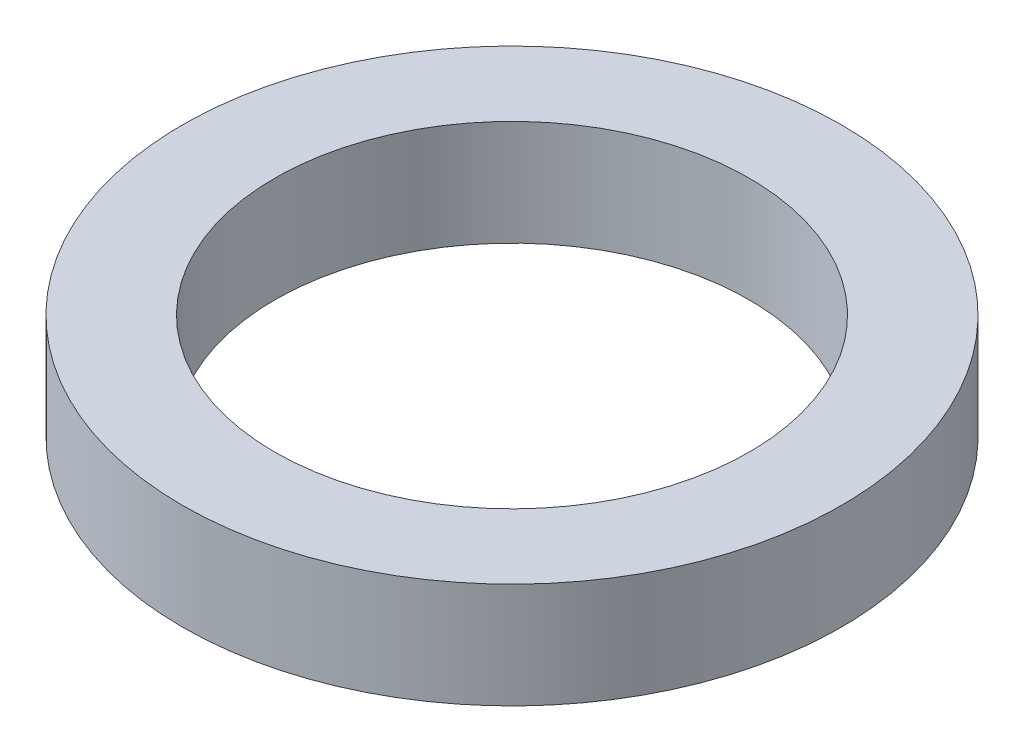
SolidWorks part; units mm, degrees
ref_plane "Front Plane" through (0, 0, 0) normal (0, 0, 1) x (1, 0, 0)
ref_plane "Top Plane" through (0, 0, 0) normal (0, 1, 0) x (1, 0, 0)
ref_plane "Right Plane" through (0, 0, 0) normal (1, 0, 0) x (0, 0, -1)
sketch "Sketch1" plane through (0, 0, 0) normal (0, 1, 0) x (1, 0, 0)
  circle A0 centre (0, 0) radius 62.5
  dimension "FLANGE_OD" = 125
extrude "Boss-Extrude1" add sketch "Sketch1" along normal blind 20
sketch "Sketch2" plane through (0, 0, 0) normal (0, 1, 0) x (1, 0, 0)
  circle A0 centre (0, 0) radius 45
  dimension "BORE_D" = 90
extrude "Cut-Extrude1" cut sketch "Sketch2" along normal through all
sketch "Sketch3" plane through (0, 20, 0) normal (0, 1, 0) x (1, 0, 0)
  circle A0 centre (0, 0) radius 25.3258 construction
  circle A1 centre (-25.3258, 0) radius 2.117
  dimension "BOLT_D" = 4.2339
  dimension "BOLT_PCD" = 50.6515
extrude "Cut-Extrude2" cut sketch "Sketch3" against normal blind 18.7448 rebuild error yes
pattern_circular "CirPattern1" count 6 over 360 rebuild error yes
